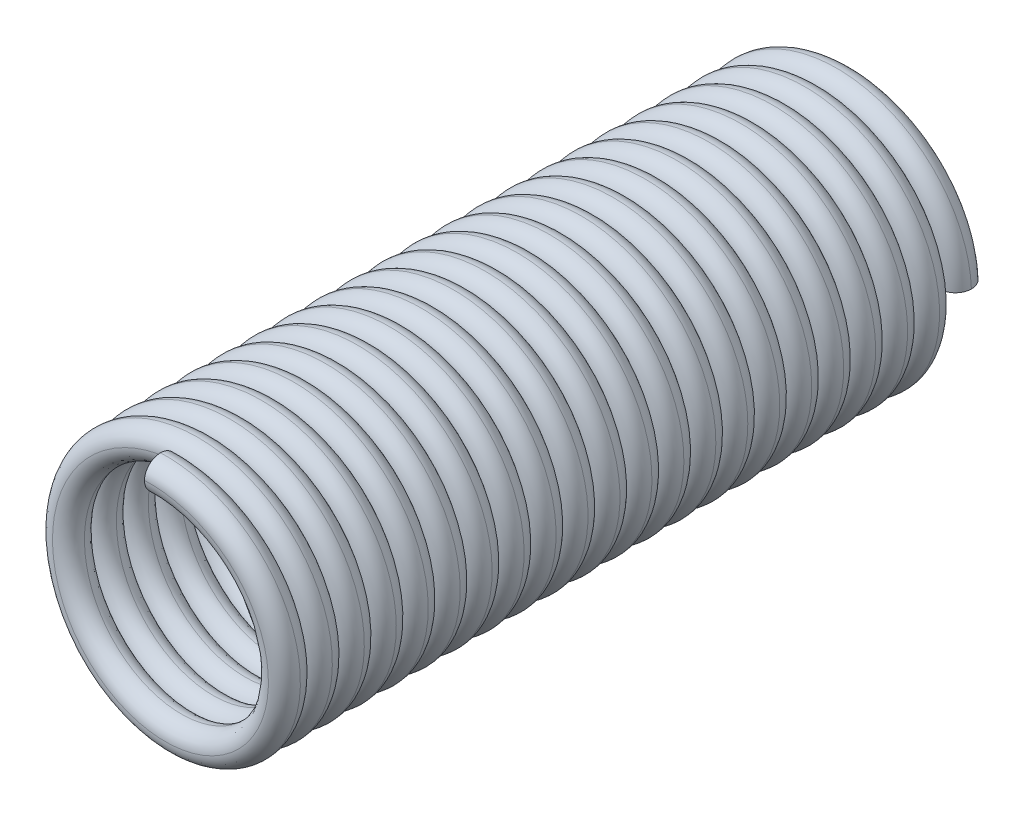
SolidWorks part; units mm, degrees
note: '?' marks a value the reader was unsure of.
ref_plane "Plan de face" through (0, 0, 0) normal (0, 0, 1) x (1, 0, 0)
ref_plane "Plan de dessus" through (0, 0, 0) normal (0, 1, 0) x (1, 0, 0)
ref_plane "Plan de droite" through (0, 0, 0) normal (1, 0, 0) x (0, 0, -1)
sketch "Esquisse2" plane through (0, 0, 0) normal (0, 0, 1) x (1, 0, 0)
  circle A0 centre (0, 0) radius 32.5
  dimension "D1" = 65
curve "Hélice/Spirale1" pitch 8 height 170 turns 21.25
ref_axis "Axe1" through (0, 0, 178.5221) along (0, 0, -1)?
ref_plane "Plan1" through (0, 0, 0) normal (0, -1, 0) x (-1, 0, 0)
sketch "Esquisse4" plane through (0, 0, 0) normal (0, -1, 0) x (-1, 0, 0)
  line L0 (0, -178.5221) -> (0, 8.9643) construction
  circle A0 centre (-29, 0) radius 4
  dimension "D2" = 8
  dimension "D1" = 29
  dimension "D3" = 0
sweep "Balayage1" add profiles "Esquisse4" path "Hélice/Spirale1"
